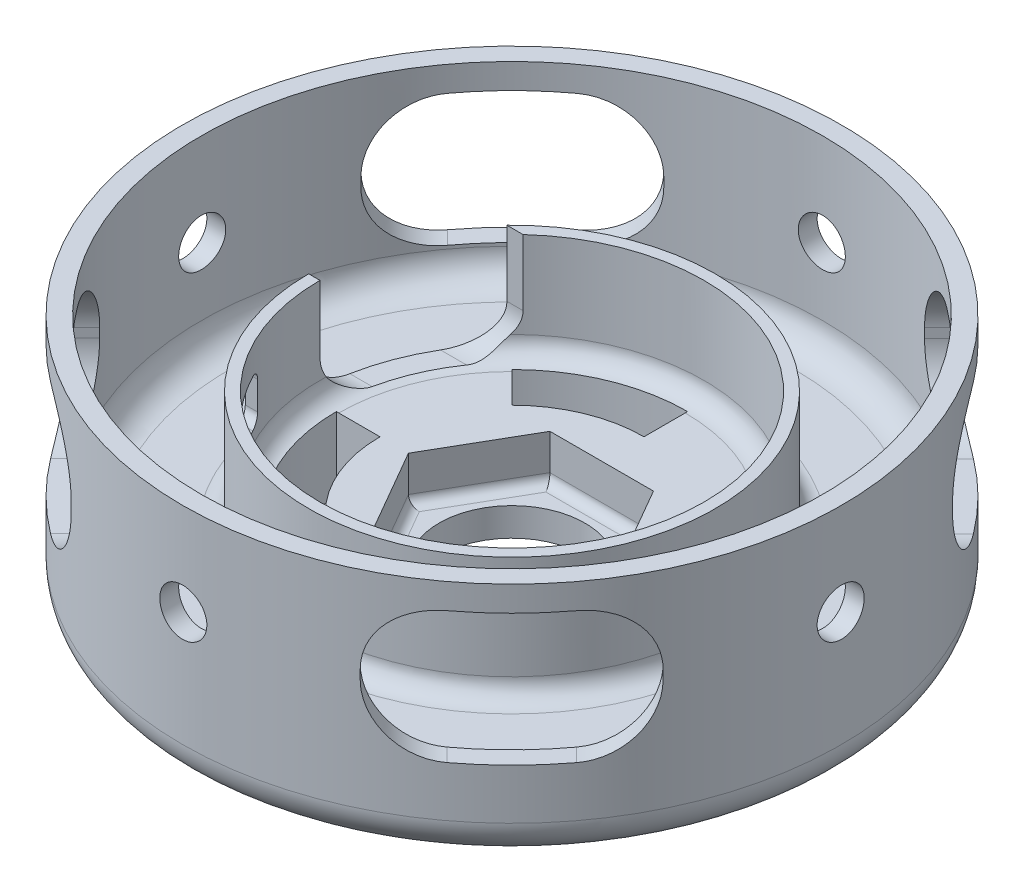
SolidWorks part; units mm, degrees
ref_plane "Front Plane" through (0, 0, 0) normal (0, 0, 1) x (1, 0, 0)
ref_plane "Top Plane" through (0, 0, 0) normal (0, 1, 0) x (1, 0, 0)
ref_plane "Right Plane" through (0, 0, 0) normal (1, 0, 0) x (0, 0, -1)
sketch "Sketch3" plane through (0, 0, 0) normal (0, 1, 0) x (1, 0, 0)
  circle A0 centre (0, 0) radius 17.5
extrude "Boss-Extrude2" add sketch "Sketch3" along normal blind 3 separate body
ref_plane "Plane1" through (0, 1.5, 0) normal (0, 1, 0) x (1, 0, 0)
sketch "Sketch6" plane through (0, 1.5, 0) normal (0, 1, 0) x (1, 0, 0)
  circle A0 centre (0, 0) radius 3.875
extrude "Cut-Extrude2" cut sketch "Sketch6" against normal blind 18
fillet "Fillet1" radius 2 1 edges at (0, 0, 17.5)
sketch "Sketch7" plane through (0, 3, 0) normal (0, 1, 0) x (1, 0, 0)
  circle A0 centre (0, 0) radius 10.8
extrude "Boss-Extrude3" add sketch "Sketch7" along normal blind 6.5
sketch "Sketch9" plane through (0, 9.5, 0) normal (0, 1, 0) x (1, 0, 0)
  circle A0 centre (0, 0) radius 10.2
extrude "Cut-Extrude3" cut sketch "Sketch9" against normal blind 5.6 contours A0
sketch "Sketch5" plane through (0, 1.5, 0) normal (0, 1, 0) x (1, 0, 0)
  line L0 (-17.5, 0) -> (17.5, 0) construction
  line L2 (5.5, 0) -> (2.75, 4.7631)
  line L3 (2.75, 4.7631) -> (-2.75, 4.7631)
  line L4 (-2.75, 4.7631) -> (-5.5, 0)
  line L5 (-5.5, 0) -> (-2.75, -4.7631)
  line L6 (-2.75, -4.7631) -> (2.75, -4.7631)
  line L7 (2.75, -4.7631) -> (5.5, 0)
  circle A0 centre (0, 0) radius 4.7631 construction
  circle A1 centre (0, 0) radius 17.5 construction
extrude "Cut-Extrude1" cut sketch "Sketch5" along normal blind 18
fillet "Fillet2" radius 1 2 edges at (0, 3.9, 10.2) (0, 3, 10.8)
ref_plane "Plane2" through (-10.8, 0, 0) normal (-1, 0, 0) x (0, 0, 1)
sketch "Sketch11" plane through (-10.8, 0, 0) normal (-1, 0, 0) x (0, 0, 1)
  line L0 (0, 9.5) -> (0, 4) construction
  line L1 (10.2, 9.5) -> (-10.2, 9.5) construction
  line L2 (10.8, 4) -> (-10.8, 4) construction
  line L3 (0, 9.5) -> (-10.8, 9.5) construction
  line L4 (-10.8, 4) -> (0, 4) construction
  line L5 (-10.8, 9.5) -> (-10.8, 4) construction
  line L7 (-7.5, 9.5) -> (-7.5, 4) construction
  line L9 (-7.5, 9.5) -> (0, 9.5)
  line L10 (-7.5, 9.5) -> (-7.5, 4)
  line L11 (-7.5, 4) -> (0, 4)
  line L12 (0, 9.5) -> (0, 4)
  dimension "D1" = 7.5
extrude "Cut-Extrude4" cut sketch "Sketch11" against normal blind 4.6 and the other way blind 9
sketch "Sketch12" plane through (-10.8, 0, 0) normal (-1, 0, 0) x (0, 0, 1)
  line L0 (0, 9.5) -> (0, 4) construction
  line L2 (4.6793, 8.0172) -> (4.2285, 8.0172)
  line L3 (4.6793, 8.0172) -> (7.7148, 8.0172)
  line L4 (4.6793, 5.5172) -> (7.7148, 5.5172)
  line L5 (4.2285, 8.0172) -> (4.2285, 5.5172)
  line L6 (4.2285, 5.5172) -> (4.6793, 5.5172)
  line L14 (7.7148, 8.0172) -> (7.7148, 5.5172)
extrude "Cut-Extrude5" cut sketch "Sketch12" against normal blind 4.6
fillet "Fillet3" radius 2 2 edges at (-6.9856, 4, -7.5) (-10.2179, 4, 0)
fillet "Fillet4" radius 0.5 4 edges at (-7.1152, 8.0172, 7.7148) (-7.1152, 5.5172, 7.7148) (-9.61, 5.5172, 4.2285) (-9.61, 8.0172, 4.2285)
sketch "Sketch14" plane through (0, 3, 0) normal (0, 1, 0) x (1, 0, 0)
  line L0 (-17.5, 0) -> (-11.8, 0) construction
  line L1 (-17.5, -2) -> (-11.8, -2) construction
  line L2 (-17.5, 2) -> (-11.8, 2) construction
  line L4 (-16.4416, 2) -> (-14.2097, 2)
  line L5 (-16.4416, 2) -> (-16.4416, -2)
  line L6 (-16.4416, -2) -> (-14.2097, -2)
  line L7 (-14.2097, 2) -> (-14.2097, -2)
  circle A1 centre (0, 0) radius 17.5 construction
  circle A2 centre (0, 0) radius 11.8 construction
  dimension "D1" = 2
  dimension "D2" = 2
extrude "Cut-Extrude6" [suppressed] cut sketch "Sketch14" against normal blind 17.6
mirror "Mirror1" [suppressed] about plane through (0, 0, 0) normal (1, 0, 0)
fillet "Fillet5" radius 0.5 6 edges at (4.125, 1.5, -2.3816) (4.125, 1.5, 2.3816) (0, 1.5, 4.7631) (-4.125, 1.5, 2.3816) (-4.125, 1.5, -2.3816) (0, 1.5, -4.7631)
sketch "Sketch15" plane through (0, 3, 0) normal (0, 1, 0) x (1, 0, 0)
  circle A0 centre (0, 0) radius 16.5
  circle A1 centre (0, 0) radius 17.5
extrude "Boss-Extrude4" add sketch "Sketch15" along normal blind 10
fillet "Fillet6" radius 1.5 1 edges at (0, 3, 16.5)
ref_plane "Plane3" through (0, 0, 17.5) normal (0, 0, 1) x (1, 0, 0)
sketch "Sketch17" plane through (0, 0, 17.5) normal (0, 0, 1) x (1, 0, 0)
  circle A0 centre (0, 8.0898) radius 1.25
extrude "Cut-Extrude7" cut sketch "Sketch17" against normal blind 3 and the other way blind 10
ref_axis "Axis1" through (0, 0, 0) along (0, 1, 0)
pattern_circular "CirPattern1" count 4 every 90 about axis through (0, 0, 0) along (0, 1, 0) of "Cut-Extrude7"
sketch "Sketch18" plane through (0, 3.9, 0) normal (0, 1, 0) x (1, 0, 0)
  line L1 (7.0101, 0) -> (9.3213, 0)
  line L3 (4.9569, 4.9569) -> (6.5912, 6.5912)
  arc A0 (9.3213, 0) -> (6.5912, 6.5912) centre (0, 0) ccw
  arc A2 (7.0101, 0) -> (4.9569, 4.9569) centre (0, 0) ccw
extrude "Cut-Extrude8" cut sketch "Sketch18" against normal blind 15 and the other way blind 15
pattern_circular "CirPattern2" count 4 over 360 about axis through (0, 0, 0) along (0, 1, 0) of "Cut-Extrude8"
ref_plane "Plane4" through (-12.3744, 0, 12.3744) normal (-0.7071, 0, 0.7071) x (0.7071, 0, 0.7071)
sketch "Sketch20" plane through (-12.3744, 0, 12.3744) normal (-0.7071, 0, 0.7071) x (0.7071, 0, 0.7071)
  line L1 (-5.7003, 11.66) -> (5.6749, 11.66)
  line L2 (-5.7003, 11.66) -> (-5.7003, 4.6723)
  line L3 (-5.7003, 4.6723) -> (5.6749, 4.6723)
  line L4 (5.6749, 11.66) -> (5.6749, 4.6723)
extrude "Cut-Extrude9" cut sketch "Sketch20" against normal blind 3
fillet "Fillet7" radius 3.25 4 edges at (-7.3179, 11.66, 15.3433) (-15.3549, 11.66, 7.2935) (-15.3549, 4.6723, 7.2935) (-7.3179, 4.6723, 15.3433)
pattern_circular "CirPattern4" count 4 every 90 about axis through (0, 0, 0) along (0, 1, 0) of "Cut-Extrude9", "Fillet7"
